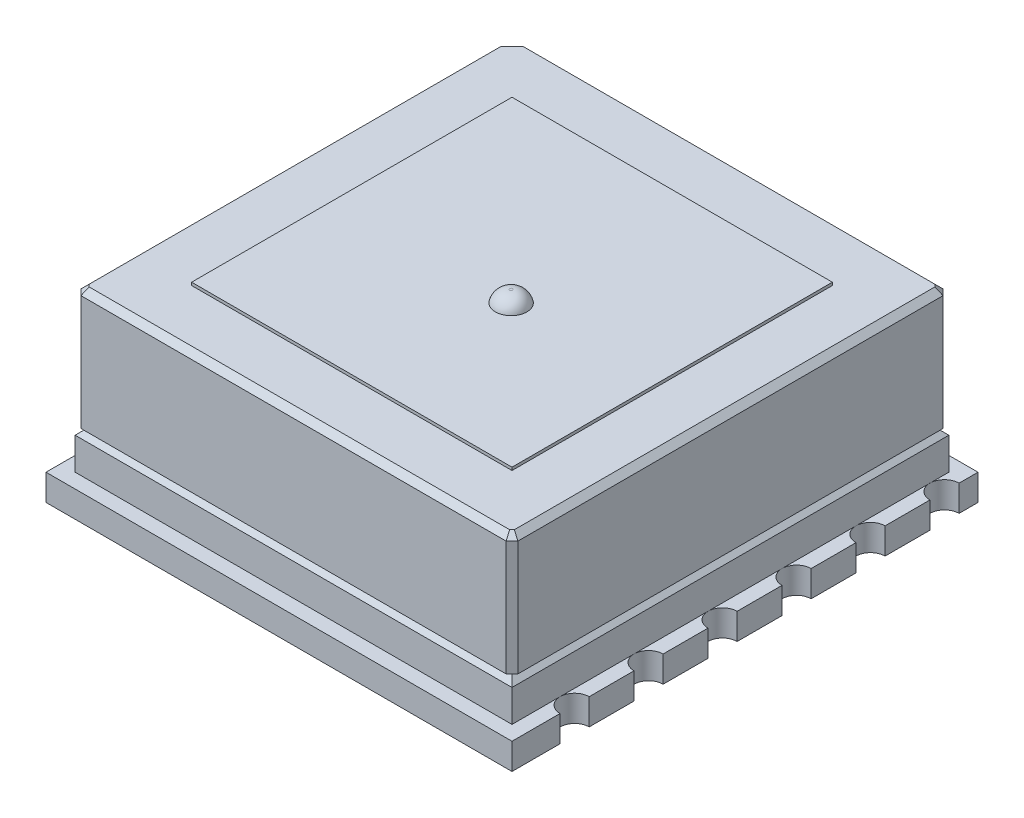
SolidWorks part; units mm, degrees
ref_plane "Спереди" through (0, 0, 0) normal (0, 0, 1) x (1, 0, 0)
ref_plane "Сверху" through (0, 0, 0) normal (0, 1, 0) x (1, 0, 0)
ref_plane "Справа" through (0, 0, 0) normal (1, 0, 0) x (0, 0, -1)
sketch "Sketch1" plane through (0, 0, 0) normal (0, 1, 0) x (1, 0, 0)
  line L0 (8, 6.35) -> (8, 4.81)
  line L1 (-8, 8) -> (8, 8)
  line L2 (-8, 8) -> (-8, 7.35)
  line L3 (-8, -8) -> (8, -8)
  line L4 (8, 8) -> (8, 7.35)
  line L5 (-8, 6.35) -> (-8, 3.81) construction
  line L6 (8, 3.81) -> (8, 2.27)
  line L7 (8, 1.27) -> (8, -0.27)
  line L8 (8, -1.27) -> (8, -2.81)
  line L9 (8, -6.35) -> (8, -8)
  line L10 (8, -3.81) -> (8, -5.35)
  line L11 (-8, -6.35) -> (-8, -8)
  line L12 (-8, -3.81) -> (-8, -5.35)
  line L13 (-8, -1.27) -> (-8, -2.81)
  line L14 (-8, 1.27) -> (-8, -0.27)
  line L15 (-8, 3.81) -> (-8, 2.27)
  line L16 (-8, 6.35) -> (-8, 4.81)
  arc A0 (-8, 6.35) -> (-8, 7.35) centre (-8, 6.85) ccw
  arc A1 (-8, 3.81) -> (-8, 4.81) centre (-8, 4.31) ccw
  arc A2 (-8, 1.27) -> (-8, 2.27) centre (-8, 1.77) ccw
  arc A3 (-8, -1.27) -> (-8, -0.27) centre (-8, -0.77) ccw
  arc A4 (-8, -3.81) -> (-8, -2.81) centre (-8, -3.31) ccw
  arc A5 (-8, -6.35) -> (-8, -5.35) centre (-8, -5.85) ccw
  arc A6 (8, 7.35) -> (8, 6.35) centre (8, 6.85) ccw
  arc A7 (8, 4.81) -> (8, 3.81) centre (8, 4.31) ccw
  arc A8 (8, 2.27) -> (8, 1.27) centre (8, 1.77) ccw
  arc A9 (8, -0.27) -> (8, -1.27) centre (8, -0.77) ccw
  arc A10 (8, -2.81) -> (8, -3.81) centre (8, -3.31) ccw
  arc A11 (8, -5.35) -> (8, -6.35) centre (8, -5.85) ccw
  dimension "D5" = 1.15
  dimension "D7" = 2.54
  dimension "D8" = 6
  dimension "D1" = 8
  dimension "D2" = 16
  dimension "D3" = 8
  dimension "D4" = 16
  dimension "D6" = 6
extrude "Extrude1" add sketch "Sketch1" along normal blind 0.9
sketch "Sketch2" plane through (0, 0.9, 0) normal (0, 1, 0) x (1, 0, 0)
  line L1 (-7.5, 7.5) -> (7.5, 7.5)
  line L2 (-7.5, 7.5) -> (-7.5, -7.5)
  line L3 (-7.5, -7.5) -> (7.5, -7.5)
  line L4 (7.5, 7.5) -> (7.5, -7.5)
  dimension "D1" = 7.5
  dimension "D2" = 15
  dimension "D3" = 7.5
  dimension "D4" = 15
extrude "Extrude2" add sketch "Sketch2" along normal blind 1.4
chamfer "Chamfer1" distance 0.3 angle 45 4 edges at (0, 2.3, -7.5) (7.5, 2.3, 0) (-7.5, 2.3, 0) (0, 2.3, 7.5)
sketch "Sketch3" plane through (0, 2.3, 0) normal (0, 1, 0) x (1, 0, 0)
  line L1 (-7.5, 7.5) -> (7.5, 7.5)
  line L2 (-7.5, 7.5) -> (-7.5, -7.5)
  line L3 (-7.5, -7.5) -> (7.5, -7.5)
  line L4 (7.5, 7.5) -> (7.5, -7.5)
  dimension "D1" = 15
  dimension "D2" = 15
  dimension "D3" = 7.5
  dimension "D4" = 7.5
extrude "Extrude3" add sketch "Sketch3" along normal blind 4.15
chamfer "Chamfer2" distance 0.5 angle 45 1 edges at (-7.5, 4.375, -7.5)
chamfer "Chamfer3" distance 0.2 angle 45 3 edges at (7.5, 4.375, -7.5) (7.5, 4.375, 7.5) (-7.5, 4.375, 7.5)
chamfer "Chamfer4" distance 0.2 angle 45 8 edges at (7.4, 6.45, 7.4) (0, 6.45, 7.5) (-7.4, 6.45, 7.4) (-7.5, 6.45, 0.15) (-7.25, 6.45, -7.25) (0.15, 6.45, -7.5) (7.4, 6.45, -7.4) (7.5, 6.45, 0)
sketch "Sketch4" plane through (0, 6.45, 0) normal (0, 1, 0) x (1, 0, 0)
  line L0 (8, -8) -> (8, 9.0614) construction
  line L1 (8, -8) -> (-10.9067, -8) construction
  circle A0 centre (0.6, -0.63) radius 0.55
  dimension "D1" = 7.4
  dimension "D2" = 7.37
extrude "Extrude4" add sketch "Sketch4" along normal blind 0.5
fillet "Fillet1" radius 0.5 1 edges at (0.6, 6.95, 1.18)
sketch "Sketch5" plane through (0, 6.45, 0) normal (0, 1, 0) x (1, 0, 0)
  line L1 (-5.5, 5.5) -> (5.5, 5.5)
  line L2 (-5.5, 5.5) -> (-5.5, -5.5)
  line L3 (-5.5, -5.5) -> (5.5, -5.5)
  line L4 (5.5, 5.5) -> (5.5, -5.5)
  dimension "D1" = 11
  dimension "D2" = 11
  dimension "D3" = 5.5
  dimension "D4" = 5.5
extrude "Extrude5" add sketch "Sketch5" along normal blind 0.1
